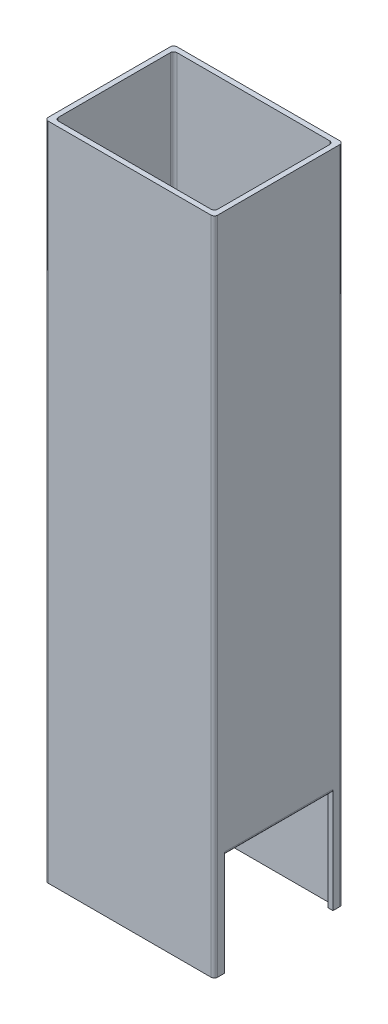
SolidWorks part; units mm, degrees
ref_plane "Front Plane" through (0, 0, 0) normal (0, 0, 1) x (1, 0, 0)
ref_plane "Top Plane" through (0, 0, 0) normal (0, 1, 0) x (1, 0, 0)
ref_plane "Right Plane" through (0, 0, 0) normal (1, 0, 0) x (0, 0, -1)
sketch "Sketch1" plane through (0, 0, 0) normal (0, 1, 0) x (1, 0, 0)
  line L0 (-30, 0) -> (0, 0) construction
  line L1 (-30, -30) -> (30, -30) construction
  line L2 (-30, -30) -> (-30, 30) construction
  line L3 (-30, 30) -> (30, 30) construction
  line L4 (30, -30) -> (30, 30) construction
  line L5 (-30, -30) -> (30, 30) construction
  line L6 (-30, 30) -> (30, -30) construction
  line L7 (0, 0) -> (30, 0) construction
  line L8 (0, 35) -> (0, -35) construction
  line L9 (-47, 35) -> (47, 35)
  line L10 (-47, 35) -> (-47, -35)
  line L11 (-47, -35) -> (47, -35)
  line L12 (47, 35) -> (47, -35)
  line L13 (-47, 0) -> (0, 0) construction
  line L14 (0, 0) -> (47, 0) construction
  line L15 (-50, 38) -> (-50, -38)
  line L16 (-50, -38) -> (50, -38)
  line L17 (50, 38) -> (50, -38)
  line L18 (-50, 38) -> (50, 38)
  point P0 (0, 0)
  point P17 (0, 0)
  point P19 (0, 0)
  dimension "D1" = 60
  dimension "D2" = 60
  dimension "D3" = 70
  dimension "D4" = 94
  dimension "D5" = 3
extrude "Boss-Extrude1" add sketch "Sketch1" along normal blind 389.5
sketch "Sketch4" plane through (0, 0, 0) normal (1, 0, 0) x (0, 0, -1)
  line L0 (-38, 0) -> (38, 0) construction
  line L1 (-32, 0) -> (32, 0)
  line L2 (-32, 0) -> (-32, 60)
  line L3 (-32, 60) -> (32, 60)
  line L4 (32, 0) -> (32, 60)
  point P6 (0, 0)
  dimension "D1" = 64
  dimension "D2" = 60
extrude "Cut-Extrude1" cut sketch "Sketch4" against normal through all and the other way through all
fillet "Fillet1" radius 2 12 edges at (47, 194.75, 35) (-47, 194.75, 35) (50, 194.75, -38) (-50, 194.75, -38) (-50, 194.75, 38) (50, 194.75, 38) (47, 194.75, -35) (-47, 194.75, -35) (-50, 60, 0) (-47, 60, 0) (50, 60, 0) (47, 60, 0)
